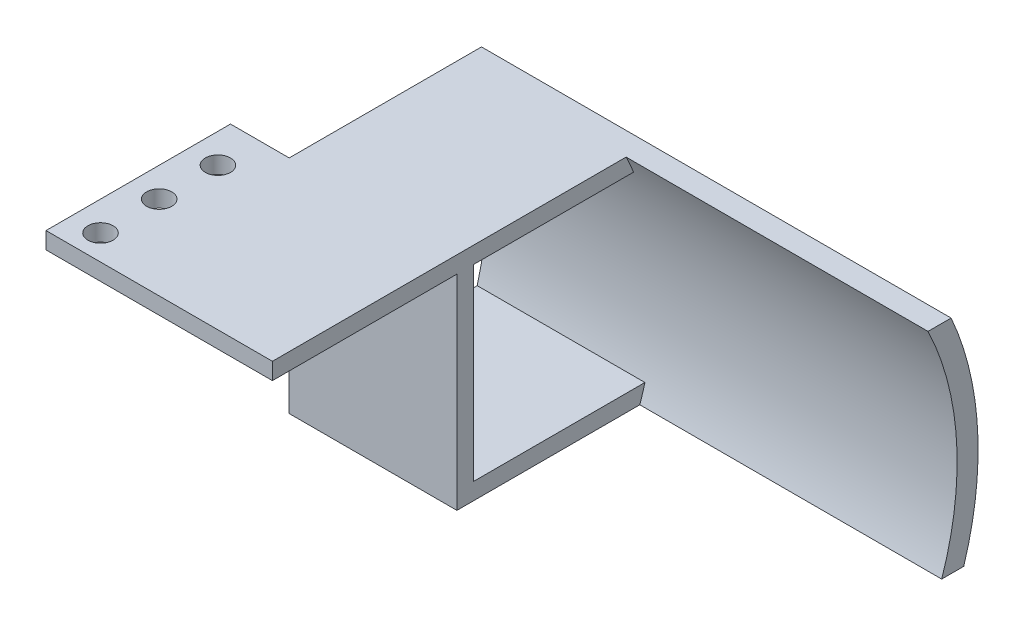
SolidWorks part; units mm, degrees
ref_plane "Front Plane" through (0, 0, 0) normal (0, 0, 1) x (1, 0, 0)
ref_plane "Top Plane" through (0, 0, 0) normal (0, 1, 0) x (1, 0, 0)
ref_plane "Right Plane" through (0, 0, 0) normal (1, 0, 0) x (0, 0, -1)
sketch "Sketch3" plane through (0, 13.2, 0) normal (0, 1, 0) x (1, 0, 0)
  line L1 (21, 49.85) -> (48, 49.85)
  line L2 (21, 49.85) -> (21, 71.85)
  line L3 (21, 71.85) -> (48, 71.85)
  line L4 (48, 49.85) -> (48, 71.85)
  line L5 (48, 69.85) -> (48, -70) construction
  line L6 (46, 71.85) -> (-46, 71.85) construction
  circle A0 centre (24.5, 59.85) radius 1.5 construction
  circle A1 centre (24.5, 66.85) radius 1.5 construction
  circle A2 centre (24.5, 59.85) radius 1.5
  circle A3 centre (24.5, 66.85) radius 1.5
  circle A4 centre (24.5, 52.85) radius 1.5 construction
  circle A5 centre (24.5, 52.85) radius 1.5
  dimension "D1" = 27
  dimension "D2" = 22
extrude "Boss-Extrude5" add sketch "Sketch3" along normal blind 2
ref_plane "Plane1" through (28, 0, 0) normal (-1, 0, 0) x (0, 0, 1)
sketch "Sketch4" plane through (28, 0, 0) normal (-1, 0, 0) x (0, 0, 1)
  line L0 (-71.85, 15.2) -> (-71.85, -11.2)
  line L3 (-71.85, -11.2) -> (-67, -11.2)
  line L4 (-71.85, 15.2) -> (-94.7813, 15.2)
  line L5 (-71.85, -11.2) -> (-96.2884, -11.2)
  line L6 (-73.85, 13.2) -> (-92.9154, 13.2)
  line L7 (-73.85, 15.2) -> (-73.85, -11.2)
  line L8 (-73.85, -9.2) -> (-94.2692, -9.2)
  arc A0 (-92.0271, 15.2) -> (-93.6596, -11.2) centre (-60.5, 0) ccw
  arc A1 (-94.7813, 15.2) -> (-96.2884, -11.2) centre (-60.5, 0) ccw
  dimension "D1" = 70
  dimension "D2" = 75
  dimension "D3" = 2
  dimension "D4" = 2
  dimension "D5" = 2
extrude "Boss-Extrude6" add sketch "Sketch4" against normal blind 20 contours L4 L7 L5 L0 | L4 A0 L6 L7 | L8 A0 L5 L7 region at (28, 2, -72.85) region at (28, 14.1921, -83.1686) region at (28, -10.195, -83.9134)
extrude "Boss-Extrude7" add sketch "Sketch4<3>" against normal blind 56 contours L4 A1 L5 A0 region at (28, 2.0986, -95.85)
sketch "Sketch4<3>" plane through (28, 0, 0) normal (-1, 0, 0) x (0, 0, 1) same geometry as "Sketch4"
